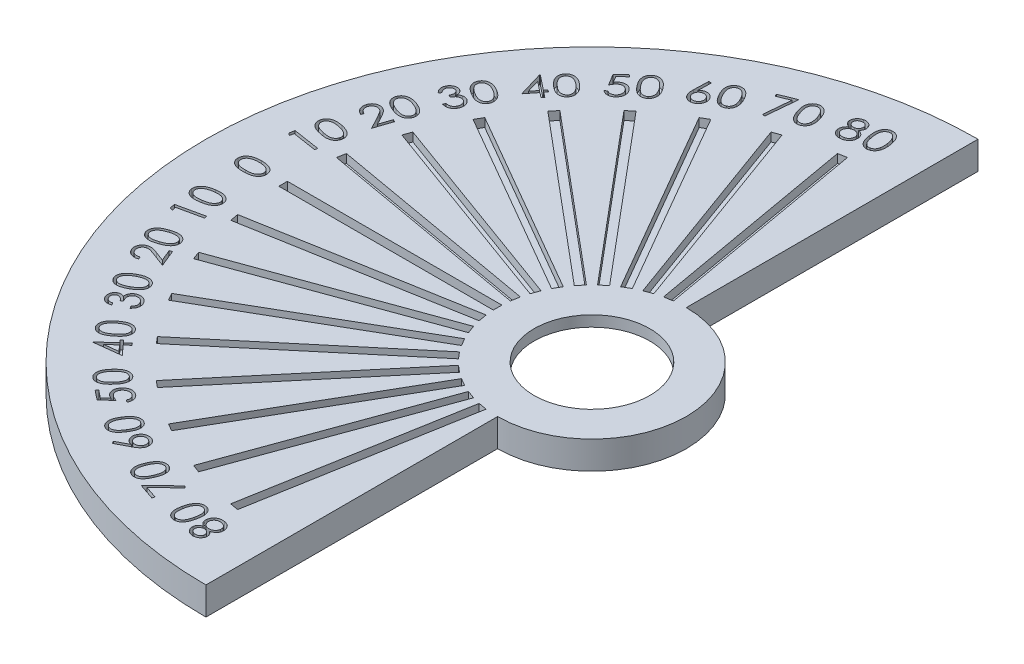
SolidWorks part; units mm, degrees
note: The reader was unsure of these and kept them because the rebuilt part matched: shared geometry of "Sketch1<6>".
ref_plane "Front Plane" through (0, 0, 0) normal (0, 0, 1) x (1, 0, 0)
ref_plane "Top Plane" through (0, 0, 0) normal (0, 1, 0) x (1, 0, 0)
ref_plane "Right Plane" through (0, 0, 0) normal (1, 0, 0) x (0, 0, -1)
sketch "Sketch1" plane through (0, 0, 0) normal (0, 1, 0) x (1, 0, 0)
  line L12 (0, 9.25) -> (0, -9.25) construction
  line L13 (-24.5826, 9.25) -> (-3.7997, 9.25)
  line L14 (-24.5826, -9.25) -> (-24.5826, -5.7126)
  line L15 (-24.5826, -9.25) -> (-3.7997, -9.25)
  line L16 (-24.5826, -5.7126) -> (-24.5826, 5.7126) construction
  line L17 (-25.5826, 10) -> (-4.5826, 10)
  line L18 (-25.5826, -10) -> (-25.5826, -5.6874)
  line L19 (-25.5826, -10) -> (-4.5826, -10)
  line L20 (-25.5826, 10) -> (-25.5826, 5.6874)
  line L21 (-24.5826, 9.25) -> (-24.5826, 5.7126)
  circle A1 centre (0, 0) radius 6.75
  arc A3 (-24.5826, -5.7126) -> (-24.5826, 5.7126) centre (-20.6435, 0) cw
  arc A4 (-25.5826, -5.6874) -> (-25.5826, 5.6874) centre (-20.6435, 0) cw
  arc A7 (-4.5826, -10) -> (-4.5826, 10) centre (0, 0) ccw
  arc A8 (-3.7997, -9.25) -> (-3.7997, 9.25) centre (0, 0) ccw
  point P0 (0, 0)
  point P2 (0, 0)
  point P12 (-24.5826, 0)
  point P14 (-27.5826, 0)
  dimension "D1" = 13.5
  dimension "D2" = 21
  dimension "D6" = 1
  dimension "D5" = 3
  dimension "D4" = 1
  dimension "D3" = 18.5
extrude "Boss-Extrude1" add sketch "Sketch1" along normal blind 1.25 contours L15 A8 L13 L21 A3 L14 A1
extrude "Boss-Extrude2" add sketch "Sketch1<6>" against normal blind 2 and the other way blind 1.25 contours L19 A7 L17 L20 A4 L18 A8 L15 L14 A3 L21 L13
sketch "Sketch1<6>" plane through (0, 0, 0) normal (0, 1, 0) x (1, 0, 0) same geometry as "Sketch1"
sketch "Sketch5" plane through (0, 1.25, 0) normal (0, 1, 0) x (1, 0, 0)
  line L1 (0, -45) -> (0, 45)
  arc A0 (0, -45) -> (0, 45) centre (0, 0) cw
  point P3 (-45, 0)
  dimension "D1" = 45
extrude "Boss-Extrude6" add sketch "Sketch5" against normal up to surface (3.25 mm away)
sketch "Sketch6" plane through (0, 1.25, 0) normal (0, 1, 0) x (1, 0, 0)
  line L0 (0, 0) -> (0, 45)
  line L4 (0, 0) -> (0, -45)
  line L6 (0, 0) -> (-7.8142, -44.3163)
  line L7 (0, 0) -> (-15.3909, -42.2862)
  line L8 (0, 0) -> (-22.5, -38.9711)
  line L9 (0, 0) -> (-28.9254, -34.472)
  line L10 (0, 0) -> (-34.472, -28.9254)
  line L11 (0, 0) -> (-38.9711, -22.5)
  line L12 (0, 0) -> (-42.2862, -15.3909)
  line L13 (0, 0) -> (-44.3163, -7.8142)
  line L14 (0, 0) -> (-45, 0)
  line L15 (0, 0) -> (-44.3163, 7.8142)
  line L16 (0, 0) -> (-42.2862, 15.3909)
  line L17 (0, 0) -> (-38.9711, 22.5)
  line L18 (0, 0) -> (-34.472, 28.9254)
  line L19 (0, 0) -> (-28.9254, 34.472)
  line L20 (0, 0) -> (-22.5, 38.9711)
  line L21 (0, 0) -> (-15.3909, 42.2862)
  line L22 (0, 0) -> (-7.8142, 44.3163)
  arc A0 (0, 45) -> (0, -45) centre (0, 0) ccw construction
  arc A3 (0, -38) -> (0, 38) centre (0, 0) cw
sketch "Sketch8" plane through (0, 1.25, 0) normal (0, 1, 0) x (1, 0, 0)
  text T0 "   80 70 60 50 40 30 20 10  0  10 20 30 40 50 60 70 80   " font "Century Gothic" height in points 12
extrude "Cut-Extrude4" cut sketch "Sketch8" against normal blind 1
sketch "Sketch15" plane through (0, 1.25, 0) normal (0, 1, 0) x (1, 0, 0)
  line L0 (-11, 0) -> (-36, 0) construction
  line L1 (-10.9197, 1.4177) -> (-10.7461, 2.4025)
  line L2 (-11, -0.5) -> (-36, -0.5)
  line L3 (-11, -0.5) -> (-11, 0.5)
  line L4 (-11, 0.5) -> (-36, 0.5)
  line L5 (-36, -0.5) -> (-36, 0.5)
  line L6 (-23.5, 0.5) -> (-23.5, -0.5) construction
  line L7 (-11, 0) -> (-36, 0) construction
  line L8 (-10.9197, 1.4177) -> (-35.5399, 5.7589)
  line L9 (-35.5399, 5.7589) -> (-35.3663, 6.7437)
  line L10 (-10.7461, 2.4025) -> (-35.3663, 6.7437)
  line L11 (-10.5076, 3.2924) -> (-10.1656, 4.2321)
  line L12 (-10.5076, 3.2924) -> (-33.9999, 11.8429)
  line L13 (-33.9999, 11.8429) -> (-33.6579, 12.7826)
  line L14 (-10.1656, 4.2321) -> (-33.6579, 12.7826)
  line L15 (-9.7763, 5.067) -> (-9.2763, 5.933)
  line L16 (-9.7763, 5.067) -> (-31.4269, 17.567)
  line L17 (-31.4269, 17.567) -> (-30.9269, 18.433)
  line L18 (-9.2763, 5.933) -> (-30.9269, 18.433)
  line L19 (-8.7479, 6.6876) -> (-8.1051, 7.4537)
  line L20 (-8.7479, 6.6876) -> (-27.899, 22.7573)
  line L21 (-27.899, 22.7573) -> (-27.2562, 23.5234)
  line L22 (-8.1051, 7.4537) -> (-27.2562, 23.5234)
  line L23 (-7.4537, 8.1051) -> (-6.6876, 8.7479)
  line L24 (-7.4537, 8.1051) -> (-23.5234, 27.2562)
  line L25 (-23.5234, 27.2562) -> (-22.7573, 27.899)
  line L26 (-6.6876, 8.7479) -> (-22.7573, 27.899)
  line L27 (-5.933, 9.2763) -> (-5.067, 9.7763)
  line L28 (-5.933, 9.2763) -> (-18.433, 30.9269)
  line L29 (-18.433, 30.9269) -> (-17.567, 31.4269)
  line L30 (-5.067, 9.7763) -> (-17.567, 31.4269)
  line L31 (-4.2321, 10.1656) -> (-3.2924, 10.5076)
  line L32 (-4.2321, 10.1656) -> (-12.7826, 33.6579)
  line L33 (-12.7826, 33.6579) -> (-11.8429, 33.9999)
  line L34 (-3.2924, 10.5076) -> (-11.8429, 33.9999)
  line L35 (-2.4025, 10.7461) -> (-1.4177, 10.9197)
  line L36 (-2.4025, 10.7461) -> (-6.7437, 35.3663)
  line L37 (-6.7437, 35.3663) -> (-5.7589, 35.5399)
  line L38 (-1.4177, 10.9197) -> (-5.7589, 35.5399)
  line L39 (-0.5, 11) -> (0.5, 11) [skipped]
  line L40 (-0.5, 11) -> (-0.5, 36) [skipped]
  line L41 (-0.5, 36) -> (0.5, 36) [skipped]
  line L42 (0.5, 11) -> (0.5, 36) [skipped]
  line L43 (1.4177, 10.9197) -> (2.4025, 10.7461) [skipped]
  line L44 (1.4177, 10.9197) -> (5.7589, 35.5399) [skipped]
  line L45 (5.7589, 35.5399) -> (6.7437, 35.3663) [skipped]
  line L46 (2.4025, 10.7461) -> (6.7437, 35.3663) [skipped]
  line L47 (3.2924, 10.5076) -> (4.2321, 10.1656) [skipped]
  line L48 (3.2924, 10.5076) -> (11.8429, 33.9999) [skipped]
  line L49 (11.8429, 33.9999) -> (12.7826, 33.6579) [skipped]
  line L50 (4.2321, 10.1656) -> (12.7826, 33.6579) [skipped]
  line L51 (5.067, 9.7763) -> (5.933, 9.2763) [skipped]
  line L52 (5.067, 9.7763) -> (17.567, 31.4269) [skipped]
  line L53 (17.567, 31.4269) -> (18.433, 30.9269) [skipped]
  line L54 (5.933, 9.2763) -> (18.433, 30.9269) [skipped]
  line L55 (6.6876, 8.7479) -> (7.4537, 8.1051) [skipped]
  line L56 (6.6876, 8.7479) -> (22.7573, 27.899) [skipped]
  line L57 (22.7573, 27.899) -> (23.5234, 27.2562) [skipped]
  line L58 (7.4537, 8.1051) -> (23.5234, 27.2562) [skipped]
  line L59 (8.1051, 7.4537) -> (8.7479, 6.6876) [skipped]
  line L60 (8.1051, 7.4537) -> (27.2562, 23.5234) [skipped]
  line L61 (27.2562, 23.5234) -> (27.899, 22.7573) [skipped]
  line L62 (8.7479, 6.6876) -> (27.899, 22.7573) [skipped]
  line L63 (9.2763, 5.933) -> (9.7763, 5.067) [skipped]
  line L64 (9.2763, 5.933) -> (30.9269, 18.433) [skipped]
  line L65 (30.9269, 18.433) -> (31.4269, 17.567) [skipped]
  line L66 (9.7763, 5.067) -> (31.4269, 17.567) [skipped]
  line L67 (10.1656, 4.2321) -> (10.5076, 3.2924) [skipped]
  line L68 (10.1656, 4.2321) -> (33.6579, 12.7826) [skipped]
  line L69 (33.6579, 12.7826) -> (33.9999, 11.8429) [skipped]
  line L70 (10.5076, 3.2924) -> (33.9999, 11.8429) [skipped]
  line L71 (10.7461, 2.4025) -> (10.9197, 1.4177) [skipped]
  line L72 (10.7461, 2.4025) -> (35.3663, 6.7437) [skipped]
  line L73 (35.3663, 6.7437) -> (35.5399, 5.7589) [skipped]
  line L74 (10.9197, 1.4177) -> (35.5399, 5.7589) [skipped]
  line L75 (11, 0.5) -> (11, -0.5) [skipped]
  line L76 (11, 0.5) -> (36, 0.5) [skipped]
  line L77 (36, 0.5) -> (36, -0.5) [skipped]
  line L78 (11, -0.5) -> (36, -0.5) [skipped]
  line L79 (10.9197, -1.4177) -> (10.7461, -2.4025) [skipped]
  line L80 (10.9197, -1.4177) -> (35.5399, -5.7589) [skipped]
  line L81 (35.5399, -5.7589) -> (35.3663, -6.7437) [skipped]
  line L82 (10.7461, -2.4025) -> (35.3663, -6.7437) [skipped]
  line L83 (10.5076, -3.2924) -> (10.1656, -4.2321) [skipped]
  line L84 (10.5076, -3.2924) -> (33.9999, -11.8429) [skipped]
  line L85 (33.9999, -11.8429) -> (33.6579, -12.7826) [skipped]
  line L86 (10.1656, -4.2321) -> (33.6579, -12.7826) [skipped]
  line L87 (9.7763, -5.067) -> (9.2763, -5.933) [skipped]
  line L88 (9.7763, -5.067) -> (31.4269, -17.567) [skipped]
  line L89 (31.4269, -17.567) -> (30.9269, -18.433) [skipped]
  line L90 (9.2763, -5.933) -> (30.9269, -18.433) [skipped]
  line L91 (8.7479, -6.6876) -> (8.1051, -7.4537) [skipped]
  line L92 (8.7479, -6.6876) -> (27.899, -22.7573) [skipped]
  line L93 (27.899, -22.7573) -> (27.2562, -23.5234) [skipped]
  line L94 (8.1051, -7.4537) -> (27.2562, -23.5234) [skipped]
  line L95 (7.4537, -8.1051) -> (6.6876, -8.7479) [skipped]
  line L96 (7.4537, -8.1051) -> (23.5234, -27.2562) [skipped]
  line L97 (23.5234, -27.2562) -> (22.7573, -27.899) [skipped]
  line L98 (6.6876, -8.7479) -> (22.7573, -27.899) [skipped]
  line L99 (5.933, -9.2763) -> (5.067, -9.7763) [skipped]
  line L100 (5.933, -9.2763) -> (18.433, -30.9269) [skipped]
  line L101 (18.433, -30.9269) -> (17.567, -31.4269) [skipped]
  line L102 (5.067, -9.7763) -> (17.567, -31.4269) [skipped]
  line L103 (4.2321, -10.1656) -> (3.2924, -10.5076) [skipped]
  line L104 (4.2321, -10.1656) -> (12.7826, -33.6579) [skipped]
  line L105 (12.7826, -33.6579) -> (11.8429, -33.9999) [skipped]
  line L106 (3.2924, -10.5076) -> (11.8429, -33.9999) [skipped]
  line L107 (2.4025, -10.7461) -> (1.4177, -10.9197) [skipped]
  line L108 (2.4025, -10.7461) -> (6.7437, -35.3663) [skipped]
  line L109 (6.7437, -35.3663) -> (5.7589, -35.5399) [skipped]
  line L110 (1.4177, -10.9197) -> (5.7589, -35.5399) [skipped]
  line L111 (0.5, -11) -> (-0.5, -11) [skipped]
  line L112 (0.5, -11) -> (0.5, -36) [skipped]
  line L113 (0.5, -36) -> (-0.5, -36) [skipped]
  line L114 (-0.5, -11) -> (-0.5, -36) [skipped]
  line L115 (-1.4177, -10.9197) -> (-2.4025, -10.7461)
  line L116 (-1.4177, -10.9197) -> (-5.7589, -35.5399)
  line L117 (-5.7589, -35.5399) -> (-6.7437, -35.3663)
  line L118 (-2.4025, -10.7461) -> (-6.7437, -35.3663)
  line L119 (-3.2924, -10.5076) -> (-4.2321, -10.1656)
  line L120 (-3.2924, -10.5076) -> (-11.8429, -33.9999)
  line L121 (-11.8429, -33.9999) -> (-12.7826, -33.6579)
  line L122 (-4.2321, -10.1656) -> (-12.7826, -33.6579)
  line L123 (-5.067, -9.7763) -> (-5.933, -9.2763)
  line L124 (-5.067, -9.7763) -> (-17.567, -31.4269)
  line L125 (-17.567, -31.4269) -> (-18.433, -30.9269)
  line L126 (-5.933, -9.2763) -> (-18.433, -30.9269)
  line L127 (-6.6876, -8.7479) -> (-7.4537, -8.1051)
  line L128 (-6.6876, -8.7479) -> (-22.7573, -27.899)
  line L129 (-22.7573, -27.899) -> (-23.5234, -27.2562)
  line L130 (-7.4537, -8.1051) -> (-23.5234, -27.2562)
  line L131 (-8.1051, -7.4537) -> (-8.7479, -6.6876)
  line L132 (-8.1051, -7.4537) -> (-27.2562, -23.5234)
  line L133 (-27.2562, -23.5234) -> (-27.899, -22.7573)
  line L134 (-8.7479, -6.6876) -> (-27.899, -22.7573)
  line L135 (-9.2763, -5.933) -> (-9.7763, -5.067)
  line L136 (-9.2763, -5.933) -> (-30.9269, -18.433)
  line L137 (-30.9269, -18.433) -> (-31.4269, -17.567)
  line L138 (-9.7763, -5.067) -> (-31.4269, -17.567)
  line L139 (-10.1656, -4.2321) -> (-10.5076, -3.2924)
  line L140 (-10.1656, -4.2321) -> (-33.6579, -12.7826)
  line L141 (-33.6579, -12.7826) -> (-33.9999, -11.8429)
  line L142 (-10.5076, -3.2924) -> (-33.9999, -11.8429)
  line L143 (-10.7461, -2.4025) -> (-10.9197, -1.4177)
  line L144 (-10.7461, -2.4025) -> (-35.3663, -6.7437)
  line L145 (-35.3663, -6.7437) -> (-35.5399, -5.7589)
  line L146 (-10.9197, -1.4177) -> (-35.5399, -5.7589)
  circle A0 centre (0, 0) radius 11 construction
  point P10 (-23.5, 0)
  point P153 (0, 0)
extrude "Cut-Extrude7" cut sketch "Sketch15" against normal blind 1
